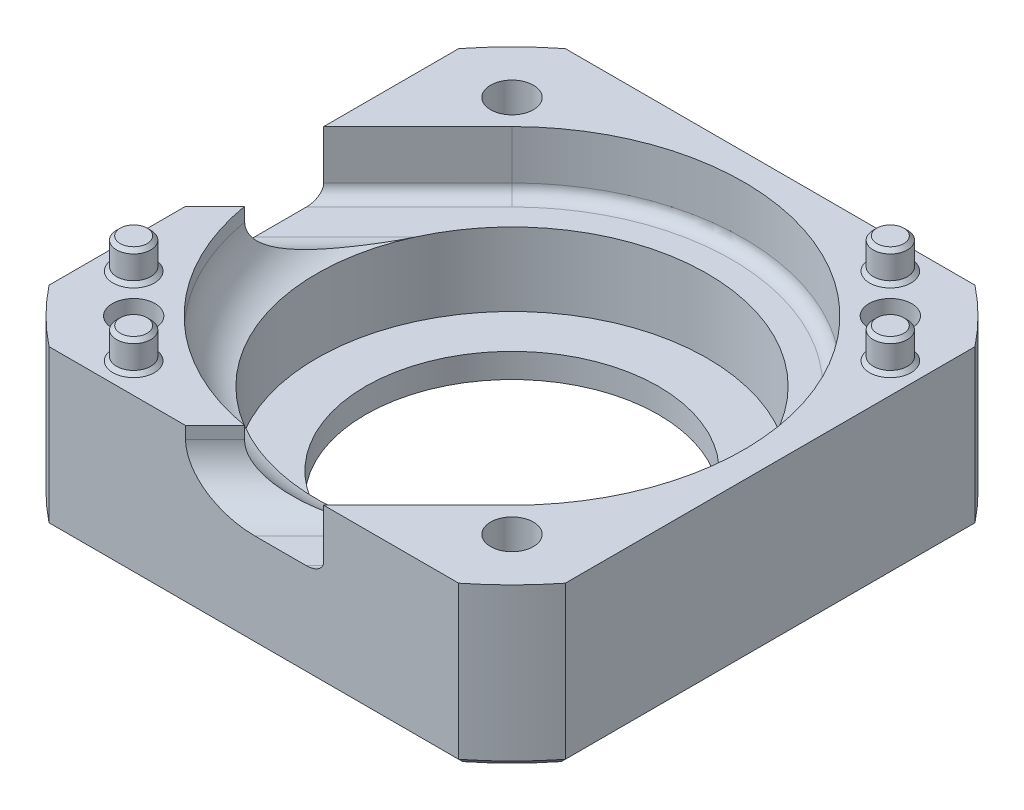
SolidWorks part; units mm, degrees
ref_plane "Front Plane" through (0, 0, 0) normal (0, 0, 1) x (1, 0, 0)
ref_plane "Top Plane" through (0, 0, 0) normal (0, 1, 0) x (1, 0, 0)
ref_plane "Right Plane" through (0, 0, 0) normal (1, 0, 0) x (0, 0, -1)
sketch "Sketch2" plane through (0, 0, 0) normal (0, 1, 0) x (1, 0, 0)
  line L1 (-21.15, 21.15) -> (21.15, 21.15)
  line L2 (-21.15, 21.15) -> (-21.15, -21.15)
  line L3 (-21.15, -21.15) -> (21.15, -21.15)
  line L4 (21.15, 21.15) -> (21.15, -21.15)
  line L5 (-21.15, 21.15) -> (21.15, -21.15) construction
  line L6 (-21.15, -21.15) -> (21.15, 21.15) construction
  point P0 (0, 0)
  dimension "D1" = 42.3
extrude "Boss-Extrude1" add sketch "Sketch2" along normal blind 13
sketch "Sketch3" plane through (0, 13, 0) normal (0, 1, 0) x (1, 0, 0)
  circle A0 centre (0, 0) radius 11
  dimension "D1" = 22
extrude "Cut-Extrude1" cut sketch "Sketch3" against normal through all
sketch "Sketch4" plane through (0, 13, 0) normal (0, 1, 0) x (1, 0, 0)
  line L1 (-15.5, 15.5) -> (15.5, 15.5) construction
  line L2 (-15.5, 15.5) -> (-15.5, -15.5) construction
  line L3 (-15.5, -15.5) -> (15.5, -15.5) construction
  line L4 (15.5, 15.5) -> (15.5, -15.5) construction
  line L5 (-15.5, 15.5) -> (15.5, -15.5) construction
  line L6 (-15.5, -15.5) -> (15.5, 15.5) construction
  circle A0 centre (-15.5, 15.5) radius 1.75
  circle A1 centre (15.5, 15.5) radius 1.75
  circle A2 centre (15.5, -15.5) radius 1.75
  circle A3 centre (-15.5, -15.5) radius 1.75
  point P0 (0, 0)
  point P16 (0, 0)
  dimension "D3" = 3.5
  dimension "D1" = 31
  dimension "D2" = 31
  dimension "D4" = 4
extrude "Cut-Extrude2" cut sketch "Sketch4" against normal through all
sketch "Sketch5" plane through (0, 13, 0) normal (0, 1, 0) x (1, 0, 0)
  circle A0 centre (0, 0) radius 27
  circle A1 centre (0, 0) radius 29.9106
  dimension "D1" = 54
extrude "Cut-Extrude4" cut sketch "Sketch5" against normal through all
sketch "Sketch6" plane through (0, 13, 0) normal (0, 1, 0) x (1, 0, 0)
  line L0 (-21.15, 5.7201) -> (-13.435, 13.435)
  line L1 (13.435, -13.435) -> (5.7201, -21.15)
  line L9 (-21.15, 16.7833) -> (-21.15, -16.7833) construction
  line L10 (-16.7833, -21.15) -> (16.7833, -21.15) construction
  line L11 (-7.7782, 7.7782) -> (-21.15, -5.5937) construction
  line L12 (5.7201, 21.15) -> (21.15, 5.7201) construction
  line L13 (7.3751, 21.15) -> (21.15, 7.3751) construction
  line L14 (16.7833, 21.15) -> (-16.7833, 21.15) construction
  line L15 (21.15, -16.7833) -> (21.15, 16.7833) construction
  line L18 (7.7782, -7.7782) -> (-5.5937, -21.15) construction
  line L19 (-21.15, 5.7201) -> (-21.15, -5.5937)
  line L21 (-3.1763, -18.7326) -> (-5.5937, -21.15)
  line L22 (-5.5937, -21.15) -> (5.7201, -21.15)
  line L23 (-18.7326, -3.1763) -> (-21.15, -5.5937)
  arc A0 (-13.435, 13.435) -> (13.435, -13.435) centre (0, 0) cw
  circle A2 centre (0, 0) radius 11 construction
  arc A4 (-13.435, 13.435) -> (13.435, -13.435) centre (0, 0) ccw construction
  circle A5 centre (15.5, 15.5) radius 1.75 construction
  arc A6 (-18.7326, -3.1763) -> (-3.1763, -18.7326) centre (0, 0) ccw
  dimension "D1" = 45
  dimension "D3" = 19
  dimension "D2" = 45
  dimension "D4" = 45
extrude "Cut-Extrude5" cut sketch "Sketch6" against normal offset from surface (11 mm away) 2 up to face at (-15.5, 0, 17.25)
sketch "Sketch7" plane through (0, 2, 0) normal (0, 1, 0) x (1, 0, 0)
  line L6 (-21.15, 5.7201) -> (-21.15, -5.5937)
  line L7 (-21.15, -5.5937) -> (-18.7326, -3.1763)
  line L8 (-3.1763, -18.7326) -> (-5.5937, -21.15)
  line L9 (-5.5937, -21.15) -> (5.7201, -21.15)
  line L10 (5.7201, -21.15) -> (13.435, -13.435)
  line L11 (-13.435, 13.435) -> (-21.15, 5.7201)
  line L12 (-21.15, 5.7201) -> (-21.15, -5.5937)
  line L13 (-21.15, -5.5937) -> (-18.7326, -3.1763)
  line L14 (-3.1763, -18.7326) -> (-5.5937, -21.15)
  line L15 (-5.5937, -21.15) -> (5.7201, -21.15)
  line L16 (5.7201, -21.15) -> (13.435, -13.435)
  line L17 (-13.435, 13.435) -> (-21.15, 5.7201)
  circle A0 centre (0, 0) radius 16
  arc A3 (-18.7326, -3.1763) -> (-3.1763, -18.7326) centre (0, 0) ccw
  arc A4 (13.435, -13.435) -> (-13.435, 13.435) centre (0, 0) ccw
  arc A5 (-18.7326, -3.1763) -> (-3.1763, -18.7326) centre (0, 0) ccw
  arc A6 (13.435, -13.435) -> (-13.435, 13.435) centre (0, 0) ccw
  dimension "D1" = 32
  dimension "D2" = 0
extrude "Boss-Extrude2" add sketch "Sketch7" along normal offset from surface (6 mm away) 5 up to face at (3.6064, 13, -3.6064)
sketch "Sketch8" plane through (0, 13, 0) normal (0, 1, 0) x (1, 0, 0)
  line L0 (12.318, 18.682) -> (18.682, 12.318) construction
  line L1 (5.7201, -21.15) -> (16.7833, -21.15) construction
  line L2 (-19.0919, 19.0919) -> (19.0919, -19.0919) construction
  line L3 (-18.682, -12.318) -> (-12.318, -18.682) construction
  circle A0 centre (15.5, 15.5) radius 1.75 construction
  circle A1 centre (12.318, 18.682) radius 1.4
  circle A2 centre (18.682, 12.318) radius 1.4
  arc A3 (-16.7833, 21.15) -> (-21.15, 16.7833) centre (0, 0) ccw construction
  arc A4 (16.7833, -21.15) -> (21.15, -16.7833) centre (0, 0) ccw construction
  circle A5 centre (-12.318, -18.682) radius 1.4
  circle A6 centre (-18.682, -12.318) radius 1.4
  point P2 (15.5, 15.5)
  dimension "D1" = 2.8
  dimension "D2" = 2.8
  dimension "D3" = 45
  dimension "D4" = 4.5
extrude "Boss-Extrude3" add sketch "Sketch8" along normal blind 2.5
chamfer "Chamfer1" distance 0.3 angle 45 4 edges at (18.682, 15.5, -10.918) (12.318, 15.5, -17.282) (-18.682, 15.5, 10.918) (-12.318, 15.5, 17.282)
chamfer "Chamfer2" distance 0.3 angle 45 4 edges at (18.682, 13, -10.918) (12.318, 13, -17.282) (-18.682, 13, 10.918) (-12.318, 13, 17.282)
sketch "Sketch9" plane through (0, 2, 0) normal (0, 1, 0) x (1, 0, 0)
  circle A0 centre (0, 0) radius 12
  dimension "D1" = 24
extrude "Cut-Extrude6" cut sketch "Sketch9" against normal through all
chamfer "Chamfer4" distance 0.5 angle 45 4 edges at (-15.5, 0, -13.75) (15.5, 0, -13.75) (-15.5, 0, 17.25) (15.5, 0, 17.25)
fillet "Fillet1" radius 4 3 edges at (-4.385, 8, 19.9413) (-19.9413, 8, 4.385) (-13.435, 8, 13.435)
chamfer "Chamfer5" distance 0.5 angle 45 8 edges at (-21.15, 0, 0) (-19.0919, 0, -19.0919) (0, 0, -21.15) (19.0919, 0, -19.0919) (21.15, 0, 0) (19.0919, 0, 19.0919) (0, 0, 21.15) (-19.0919, 0, 19.0919)
fillet "Fillet2" radius 1 3 edges at (9.5775, 8, 17.2925) (-17.2925, 8, -9.5775) (13.435, 8, -13.435)
